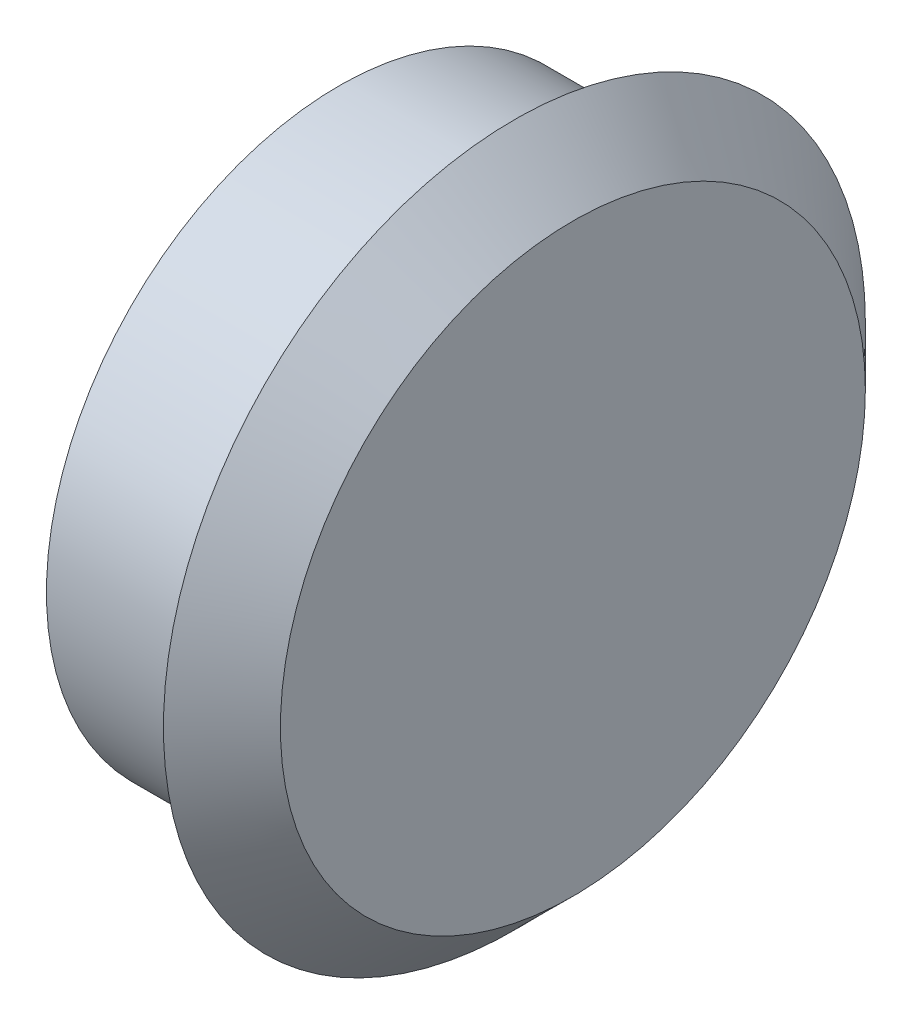
SolidWorks part; units mm, degrees
ref_plane "Спереди" through (0, 0, 0) normal (0, 0, 1) x (1, 0, 0)
ref_plane "Сверху" through (0, 0, 0) normal (0, 1, 0) x (1, 0, 0)
ref_plane "Справа" through (0, 0, 0) normal (1, 0, 0) x (0, 0, -1)
sketch "Эскиз1" plane through (0, 0, 0) normal (1, 0, 0) x (0, 0, -1)
  circle A0 centre (0, 0) radius 50
  circle A1 centre (0, 0) radius 45
  dimension "D1" = 100
  dimension "D2" = 90
extrude "Бобышка-Вытянуть1" add sketch "Эскиз1" along normal blind 30
sketch "Эскиз2" plane through (30, 0, 0) normal (1, 0, 0) x (0, 0, -1)
  circle A0 centre (0, 0) radius 60
  dimension "D1" = 120
extrude "Бобышка-Вытянуть2" add sketch "Эскиз2" along normal blind 10
chamfer "Фаска1" distance 10 angle 45 1 edges at (40, 0, -60)
